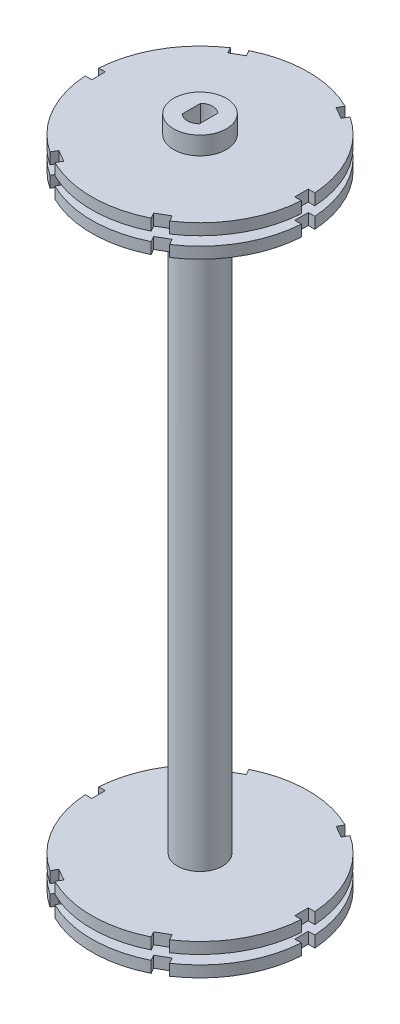
SolidWorks part; units mm, degrees
note: '?' marks a value the reader was unsure of.
ref_plane "Front Plane" through (0, 0, 0) normal (0, 0, 1) x (1, 0, 0)
ref_plane "Top Plane" through (0, 0, 0) normal (0, 1, 0) x (1, 0, 0)
ref_plane "Right Plane" through (0, 0, 0) normal (1, 0, 0) x (0, 0, -1)
sketch "Sketch1" plane through (0, 0, 0) normal (0, 1, 0) x (1, 0, 0)
  line L0 (1.9, 2.0567) -> (1.9, -2.0567)
  line L1 (-1.9, -2.0567) -> (-1.9, 2.0567)
  line L2 (-1.9, 2.0567) -> (-1.9, 5.5329)
  line L3 (1.9, 2.0567) -> (1.9, 5.5329)
  line L4 (-1.9, -2.0567) -> (-1.9, -5.5329)
  line L5 (1.9, -2.0567) -> (1.9, -5.5329)
  circle A0 centre (0, 0) radius 2.8
  circle A1 centre (0, 0) radius 5.85
  dimension "D1" = 5.6
  dimension "D4" = 11.7
  dimension "D2" = 1.9
  dimension "D3" = 1.9
extrude "Boss-Extrude1" add sketch "Sketch1" along normal blind 6.5 contours L2 A1 L4 A0 | L3 A1 L2 A0 | L5 A1 L3 A0 | L4 A1 L5 A0 | L1 A0 | L0 A0
sketch "Sketch2" plane through (0, 6.5, 0) normal (0, 1, 0) x (1, 0, 0)
  circle A0 centre (0, 0) radius 24
  dimension "D1" = 48
extrude "Boss-Extrude2" add sketch "Sketch2" against normal blind 2.5
sketch "Sketch3" plane through (0, 4, 0) normal (0, -1, 0) x (1, 0, 0)
  line L2 (-1.9, 2.0567) -> (-1.9, -2.0567)
  line L3 (1.9, -2.0567) -> (1.9, 2.0567)
  line L4 (-1.9, 2.0567) -> (-1.9, -2.0567)
  line L5 (1.9, -2.0567) -> (1.9, 2.0567)
  arc A2 (1.9, 2.0567) -> (-1.9, 2.0567) centre (0, 0) ccw
  arc A3 (-1.9, -2.0567) -> (1.9, -2.0567) centre (0, 0) ccw
  arc A4 (1.9, 2.0567) -> (-1.9, 2.0567) centre (0, 0) ccw
  arc A5 (-1.9, -2.0567) -> (1.9, -2.0567) centre (0, 0) ccw
  dimension "D1" = 0
extrude "Cut-Extrude1" cut sketch "Sketch3" against normal blind 8
sketch "Sketch4" plane through (0, 6.5, 0) normal (0, 1, 0) x (1, 0, 0)
  line L5 (-53.8948, 0) -> (53.8948, 0) construction
  line L6 (0, 31.6457) -> (0, -31.6457) construction
  line L7 (12.549, -18.7356) -> (14.049, -21.3336)
  line L9 (22.5, 1.5) -> (25.5, 1.5)
  line L10 (22.5, 1.5) -> (22.5, -1.5)
  line L11 (22.5, -1.5) -> (25.5, -1.5)
  line L12 (25.5, 1.5) -> (25.5, -1.5)
  line L13 (22.5, 1.5) -> (25.5, -1.5) construction
  line L14 (22.5, -1.5) -> (25.5, 1.5) construction
  line L29 (12.549, -18.7356) -> (9.951, -20.2356)
  line L30 (9.951, -20.2356) -> (11.451, -22.8336)
  line L35 (14.049, -21.3336) -> (11.451, -22.8336)
  line L36 (12.549, -18.7356) -> (11.451, -22.8336) construction
  line L41 (9.951, -20.2356) -> (14.049, -21.3336) construction
  line L42 (-26.9474, 46.6742) -> (26.9474, -46.6742) construction
  line L43 (-9.951, -20.2356) -> (-11.451, -22.8336)
  line L44 (-9.951, -20.2356) -> (-12.549, -18.7356)
  line L45 (-12.549, -18.7356) -> (-14.049, -21.3336)
  line L46 (-11.451, -22.8336) -> (-14.049, -21.3336)
  line L47 (-9.951, -20.2356) -> (-14.049, -21.3336) construction
  line L48 (-12.549, -18.7356) -> (-11.451, -22.8336) construction
  line L49 (26.9474, 46.6742) -> (-26.9474, -46.6742) construction
  line L50 (-22.5, -1.5) -> (-25.5, -1.5)
  line L51 (-22.5, -1.5) -> (-22.5, 1.5)
  line L52 (-22.5, 1.5) -> (-25.5, 1.5)
  line L53 (-25.5, -1.5) -> (-25.5, 1.5)
  line L54 (-22.5, -1.5) -> (-25.5, 1.5) construction
  line L55 (-22.5, 1.5) -> (-25.5, -1.5) construction
  line L56 (53.8948, 0) -> (-53.8948, 0) construction
  line L57 (-12.549, 18.7356) -> (-14.049, 21.3336)
  line L58 (-12.549, 18.7356) -> (-9.951, 20.2356)
  line L59 (-9.951, 20.2356) -> (-11.451, 22.8336)
  line L60 (-14.049, 21.3336) -> (-11.451, 22.8336)
  line L61 (-12.549, 18.7356) -> (-11.451, 22.8336) construction
  line L62 (-9.951, 20.2356) -> (-14.049, 21.3336) construction
  line L63 (26.9474, -46.6742) -> (-26.9474, 46.6742) construction
  line L64 (9.951, 20.2356) -> (11.451, 22.8336)
  line L65 (9.951, 20.2356) -> (12.549, 18.7356)
  line L66 (12.549, 18.7356) -> (14.049, 21.3336)
  line L67 (11.451, 22.8336) -> (14.049, 21.3336)
  line L68 (9.951, 20.2356) -> (14.049, 21.3336) construction
  line L69 (12.549, 18.7356) -> (11.451, 22.8336) construction
  line L70 (-26.9474, -46.6742) -> (26.9474, 46.6742) construction
  circle A0 centre (0, 0) radius 24 construction
  point P3 (0, 0)
  point P8 (0, 0)
  point P12 (24, 0)
  point P19 (12, -20.7846)
  point P26 (-12, -20.7846)
  point P33 (-24, 0)
  point P40 (-12, 20.7846)
  point P47 (12, 20.7846)
  dimension "D4" = 3
  dimension "D5" = 3
ref_axis "Axis1" through (0, 6.5, 0) along (0, -1, 0)?
extrude "Cut-Extrude2" cut sketch "Sketch4" against normal blind 10
sketch "Sketch5" plane through (0, 6.5, 0) normal (0, 1, 0) x (1, 0, 0)
  circle A0 centre (0, 0) radius 5
  dimension "D1" = 10
extrude "Boss-Extrude3" add sketch "Sketch5" along normal blind 140
ref_plane "Plane1" through (0, 76.5, 0) normal (0, 1, 0) x (1, 0, 0)
mirror "Mirror1" about plane through (0, 76.5, 0) normal (0, 1, 0) of "Boss-Extrude2"
mirror "Mirror2" about plane through (0, 76.5, 0) normal (0, 1, 0) of "Boss-Extrude1"
ref_plane "Plane2" through (0, 7.5, 0) normal (0, 1, 0) x (1, 0, 0)
mirror "Mirror3" about plane through (0, 7.5, 0) normal (0, 1, 0) of "Cut-Extrude2", "Boss-Extrude2", "Cut-Extrude1"
sketch "Sketch6" plane through (0, 11, 0) normal (0, -1, 0) x (1, 0, 0)
  line L2 (-1.9, 2.0567) -> (-1.9, -2.0567)
  line L3 (1.9, -2.0567) -> (1.9, 2.0567)
  line L4 (-1.9, 2.0567) -> (-1.9, -2.0567)
  line L5 (1.9, -2.0567) -> (1.9, 2.0567)
  arc A2 (1.9, 2.0567) -> (-1.9, 2.0567) centre (0, 0) ccw
  arc A3 (-1.9, -2.0567) -> (1.9, -2.0567) centre (0, 0) ccw
  arc A4 (1.9, 2.0567) -> (-1.9, 2.0567) centre (0, 0) ccw
  arc A5 (-1.9, -2.0567) -> (1.9, -2.0567) centre (0, 0) ccw
  dimension "D1" = 0
extrude "Cut-Extrude3" cut sketch "Sketch6" against normal blind 15
ref_plane "Plane3" through (0, 145.5, 0) normal (0, -1, 0) x (-1, 0, 0)
mirror "Mirror5" about plane through (0, 76.5, 0) normal (0, 1, 0) of "Cut-Extrude2"
mirror "Mirror6" about plane through (0, 145.5, 0) normal (0, -1, 0) of "Mirror5", "Mirror1"
sketch "Sketch7" plane through (0, 153, 0) normal (0, 1, 0) x (1, 0, 0)
